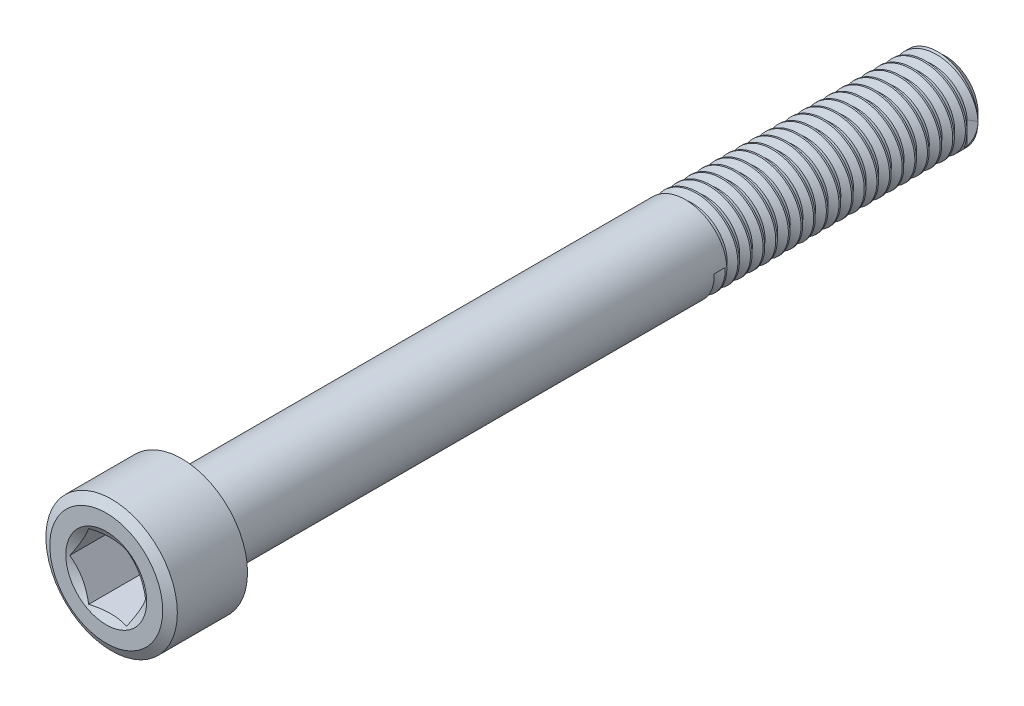
SolidWorks part; units mm, degrees
material "Stainless Steel (ferritic)"
ref_plane "Front Plane" through (0, 0, 0) normal (0, 0, 1) x (1, 0, 0)
ref_plane "Top Plane" through (0, 0, 0) normal (0, 1, 0) x (1, 0, 0)
ref_plane "Right Plane" through (0, 0, 0) normal (1, 0, 0) x (0, 0, -1)
sketch "Sketch1" plane through (0, 0, 0) normal (1, 0, 0) x (0, 0, -1)
  line L0 (0, 0) -> (66.2642, 0) construction
  line L1 (0, 0) -> (0, 5.582)
  line L2 (0, 5.582) -> (0.53, 6.5)
  line L3 (0.53, 6.5) -> (7.47, 6.5)
  line L4 (7.47, 6.5) -> (8, 5.582)
  line L5 (8, 5.582) -> (8, 4)
  line L6 (8, 4) -> (83, 4)
  line L7 (83, 4) -> (83, 0)
  line L8 (83, 0) -> (0, 0)
  dimension "D1" = 4
  dimension "D2" = 75
  dimension "D3" = 8
  dimension "D4" = 6.5
  dimension "D5" = 30
  dimension "D6" = 30
  dimension "D7" = 0.53
  dimension "D8" = 0.53
revolve "Revolve1" add sketch "Sketch1" angle 360 about L0
chamfer "Chamfer1" distance 0.8 angle 45 1 edges at (4, 0, -83)
sketch "Sketch2" plane through (0, 0, 0) normal (0, 0, 1) x (1, 0, 0)
  line L1 (-1.8764, -3.25) -> (1.8764, -3.25)
  line L2 (1.8764, -3.25) -> (3.7528, 0)
  line L3 (3.7528, 0) -> (1.8764, 3.25)
  line L4 (1.8764, 3.25) -> (-1.8764, 3.25)
  line L5 (-1.8764, 3.25) -> (-3.7528, 0)
  line L6 (-3.7528, 0) -> (-1.8764, -3.25)
  circle A0 centre (0, 0) radius 3.25 construction
  dimension "D1" = 6.5
extrude "Cut-Extrude1" cut sketch "Sketch2" against normal blind 6
sketch "Sketch3" plane through (0, 0, 0) normal (1, 0, 0) x (0, 0, -1)
  line L0 (0, 0) -> (40.9537, 0) construction
  line L1 (0, 0) -> (0, 4)
  line L2 (0, 5.582) -> (0, -5.582) construction
  line L3 (0, 4) -> (2.3094, 0)
  line L4 (2.3094, 0) -> (0, 0)
  line L5 (6, 3.25) -> (6, 0)
  line L6 (6, 0) -> (7.8764, 0)
  line L7 (7.8764, 0) -> (6, 3.25)
  dimension "D1" = 30
  dimension "D2" = 30
  dimension "D3" = 4
revolve "Cut-Revolve1" cut sketch "Sketch3" angle 360 about L0
thread "Thread1" pitch 1.25 method cut profile "Thread Profile2" start angle 0, offset 0, length 25, pitch 1.25, diameter 8
ref_plane "Plane2" through (4, 0, -82.2) normal (0, -1, 0) x (1, 0, 0)
sketch "Thread Profile2" plane through (4, 0, -82.2) normal (0, -1, 0) x (1, 0, 0)
  line L0 (0, 0) -> (0, 1.25) construction
  line L11 (0, 0) -> (0, 1.0937)
  line L12 (0, 1.0937) -> (-0.6766, 0.7031)
  line L13 (-0.6766, 0.7031) -> (-0.6766, 0.3906)
  line L15 (-0.6766, 0.3906) -> (0, 0)
  line L17 (-0.6766, 0.5469) -> (0, 0.5469) construction
  point P2 (0, 0)
  dimension "Pitch" = 1.25
  dimension "Profile_Angle" = 60
  dimension "Profile_Land" = 0.3125
  dimension "Profile_Height" = 0.6766
sketch "Sketch20" plane through (0, 0, 0) normal (0, 1, 0) x (1, 0, 0)
  line L4 (4, 82.2) -> (3.3234, 81.8094)
  line L5 (3.3234, 81.8094) -> (3.3234, 81.4969)
  line L6 (3.3234, 81.4969) -> (4, 81.1063)
  line L7 (4, 81.1063) -> (4, 82.2)
  line L8 (4, 82.2) -> (3.3234, 81.8094)
  line L9 (3.3234, 81.8094) -> (3.3234, 81.4969)
  line L10 (3.3234, 81.4969) -> (4, 81.1063)
  line L11 (4, 81.1063) -> (4, 82.2)
  dimension "D1" = 0
extrude "Cut-Extrude2" cut sketch "Sketch20" against normal blind 10
